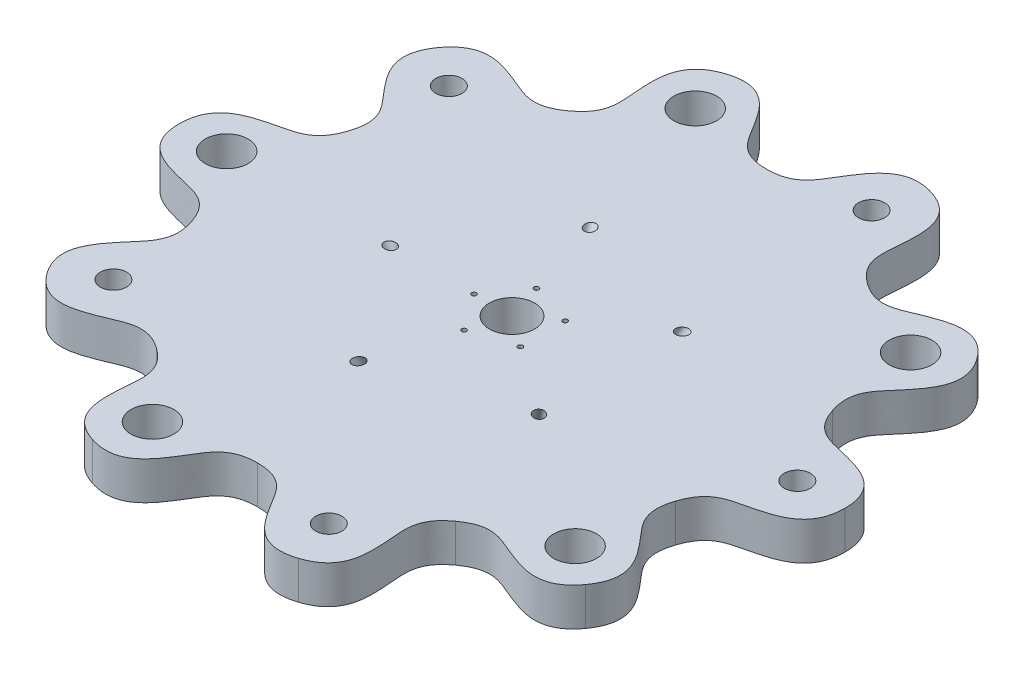
SolidWorks part; units mm, degrees
other "Markup1"
sketch "Sketch22" plane through (67.4, 16.5, 67.4) normal (0.6133, 0.6241, 0.4841) x (0.6587, -0.0661, -0.7495)
sketch "Sketch37" plane through (67.4, 28, 67.4) normal (0.6133, 0.6241, 0.4841) x (0.6587, -0.0661, -0.7495)
other "Markup2"
sketch "Sketch23" plane through (67.4, 26.5, 67.4) normal (0.1362, 0.0894, 0.9866) x (0.9893, -0.0646, -0.1307)
sketch "Sketch38" plane through (67.4, 28, 67.4) normal (0.1362, 0.0894, 0.9866) x (0.9893, -0.0646, -0.1307)
other "Markup5"
sketch "Sketch28" plane through (-67.4, 30.5, 67.4) normal (-0.0176, 0.5562, 0.8308) x (0.9998, 0.0146, 0.0115)
sketch "Sketch39" plane through (-67.4, 28, 67.4) normal (-0.0176, 0.5562, 0.8308) x (0.9998, 0.0146, 0.0115)
material "1023 Carbon Steel Sheet (SS)"
ref_plane "Front Plane" through (0, 0, 0) normal (0, 0, 1) x (1, 0, 0)
ref_plane "Top Plane" through (0, 0, 0) normal (0, 1, 0) x (1, 0, 0)
ref_plane "Right Plane" through (0, 0, 0) normal (1, 0, 0) x (0, 0, -1)
sketch "Sketch1" plane through (0, 0, 0) normal (0, 0, 1) x (1, 0, 0)
  line L5 (-47.4, 0) -> (-47.4, -8)
  line L9 (-7, -8) -> (0, -8)
  line L10 (0, -8) -> (0, 0)
  line L12 (-7, -8) -> (-17.4, -8)
  line L24 (-17.4, -8) -> (-47.4, -8)
  line L25 (-47.4, 0) -> (0, 0)
  dimension "D2" = 8
  dimension "D3" = 47.4
  dimension "D8" = 0
  dimension "D10" = 7
revolve "Revolve1" add sketch "Sketch1" angle 360 about L10
sketch "Sketch4" plane through (0, 0, 0) normal (0, 0, 1) x (1, 0, 0)
  line L0 (0, 0) -> (0, 13.3666) construction
sketch "Sketch2" plane through (0, 0, 0) normal (0, 1, 0) x (1, 0, 0)
  circle A0 centre (-8, 0) radius 0.5
  dimension "D2" = 1
  dimension "D1" = 8
extrude "Fuel holes" cut sketch "Sketch2" against normal up to next from offset 5
pattern_circular "CirPattern1" count 5 over 360 about axis through (0, 0, 0) along (0, 1, 0) of "Fuel holes" reverse direction yes
sketch "Sketch5" plane through (0, 0, 0) normal (1, 0, 0) x (0, 0, -1)
sketch "Sketch19" plane through (0, -8, 0) normal (0, -1, 0) x (1, 0, 0)
  line L0 (-47.4, 0) -> (-70, 0) construction
  line L1 (-56.6312, -41.145) -> (0, 0) construction
  line L4 (0, 0) -> (-66.574, -21.6312) construction
  line L5 (-51.8483, -13.5569) -> (-50.8815, -16.5324) construction
  line L9 (-69, 0) -> (-70, 0)
  line L11 (-53.7996, 39.0877) -> (-54.2257, 38.5013)
  circle A1 centre (0, 0) radius 47.4
  circle A2 centre (0, 0) radius 70 construction
  circle A3 centre (-60, 0) radius 4.5
  circle A4 centre (0, 0) radius 47.4 construction
  circle A5 centre (-48.541, -35.2671) radius 2.75
  circle A6 centre (0, 0) radius 53.5
  circle A8 centre (0, 0) radius 70
  spline S0 degree 3 poles (-50.8815, -16.5324) (-52.4491, -11.7078) (-59.9998, -9.5551) (-70, -7.7496) (-70, 0) knots 0 0 0 0 0.376166 1 1 1 1
  spline S1 degree 3 poles (-50.8815, -16.5324) (-49.3139, -21.357) (-54.1572, -27.5367) (-61.1863, -34.8754) (-56.6312, -41.145) knots 0 0 0 0 0.376166 1 1 1 1
  circle M22 centre (0, 0) radius 47.4
  dimension "D2" = 9
  dimension "D5" = 5.5
  dimension "D7" = 107
  dimension "D3" = 60
  dimension "D4" = 36
  dimension "D6" = 60
  dimension "D8" = 18
  dimension "D1" = 22.6
extrude "Boss-Extrude2" add sketch "Sketch19" against normal blind 8 contours A6 S1 A8 S0 A3 A5 | S1 S0 A8 | A3 | A5 | A6 M22 region at (-60, -8, 0) region at (-48.541, -8, -35.2671) region at (8.1325, -8, -51.3467) region at (-61.1052, -8, -7.4539) region at (-60.0877, -8, -19.5238)
extrude "Bolt holes" cut sketch "Sketch19<3>" against normal up to surface (8 mm away) contours A3 | A5 up to face at (-1.9721, 0, -7.6085)
sketch "Sketch19<3>" plane through (0, -8, 0) normal (0, -1, 0) x (1, 0, 0) same geometry as "Sketch19"
extrude "Grooves" cut sketch "Sketch19<8>" against normal through all contours S1 S0 A8 region at (-60.0877, -8, -19.5238)
sketch "Sketch19<8>" plane through (0, -8, 0) normal (0, -1, 0) x (1, 0, 0) same geometry as "Sketch19"
sketch "Sketch21" plane through (0, 0, 0) normal (0, 0, 1) x (1, 0, 0)
  line L0 (0, 0) -> (51.8972, 0) construction
  line L1 (0, 0) -> (0, -5.4672) construction
sketch "Sketch8" plane through (-29.8564, -8, 0) normal (0, -1, 0) x (-1, 0, 0)
  line L0 (-29.8564, 0) -> (-8.8564, 0) construction
  line L1 (-8.8564, 0) -> (-8.8564, 32.0516) construction
  circle A2 centre (-8.8564, 0) radius 1.75
  dimension "D1" = 3.5
  dimension "D2" = 21
ref_plane "Plane1" through (-21, 0, 0) normal (1, 0, 0) x (0, 0, -1)
ref_plane "Plane2" through (-1.7859, 3.0933, 0) normal (0.5, -0.866, 0) x (0, 0, -1)
sketch "Sketch41" plane through (-1.7859, 3.0933, 0) normal (0.5, -0.866, 0) x (0, 0, -1)
  circle A0 centre (0, -22.1865) radius 1.15
  dimension "D1" = 2.3
extrude "Cut-Extrude7" cut sketch "Sketch41" against normal blind 10 and the other way through all
sketch "Sketch31" plane through (0, -8, 0) normal (0, -1, 0) x (1, 0, 0)
  circle A0 centre (0, 0) radius 27.4
  dimension "D1" = 54.8
sketch "Sketch32" plane through (0, 0, 0) normal (0, 1, 0) x (1, 0, 0)
  circle A0 centre (0, 0) radius 5.5 construction
  circle A1 centre (0, 0) radius 4.75
  point P2 (0, 0)
  dimension "M11_threads" = 11
  dimension "M11Tap" = 9.5
sketch "Sketch35" plane through (0, 0, 0) normal (0, 0, 1) x (1, 0, 0)
  line L0 (0, 0) -> (0, 22.3821) construction
pattern_circular "CirPattern9" count 5 over 360 about axis through (0, 0, 0) along (0, 1, 0) of "Cut-Extrude7"
pattern_circular "CirPattern10" count 5 over 360 about axis through (0, 0, 0) along (0, 1, 0) of "Bolt holes"
pattern_circular "CirPattern11" count 10 over 360 about axis through (0, 0, 0) along (0, 1, 0) of "Grooves"
extrude "M11Tap" cut sketch "Sketch32" against normal through all contours A1
equation "\"Bolts\"= 10"
equation "\"D4@Sketch19\"=360/\"Bolts\""
equation "\"D7@Sketch19\"=102+2.5*2"
equation "\"D8@Sketch19\"=\"D4@Sketch19\"/2"
